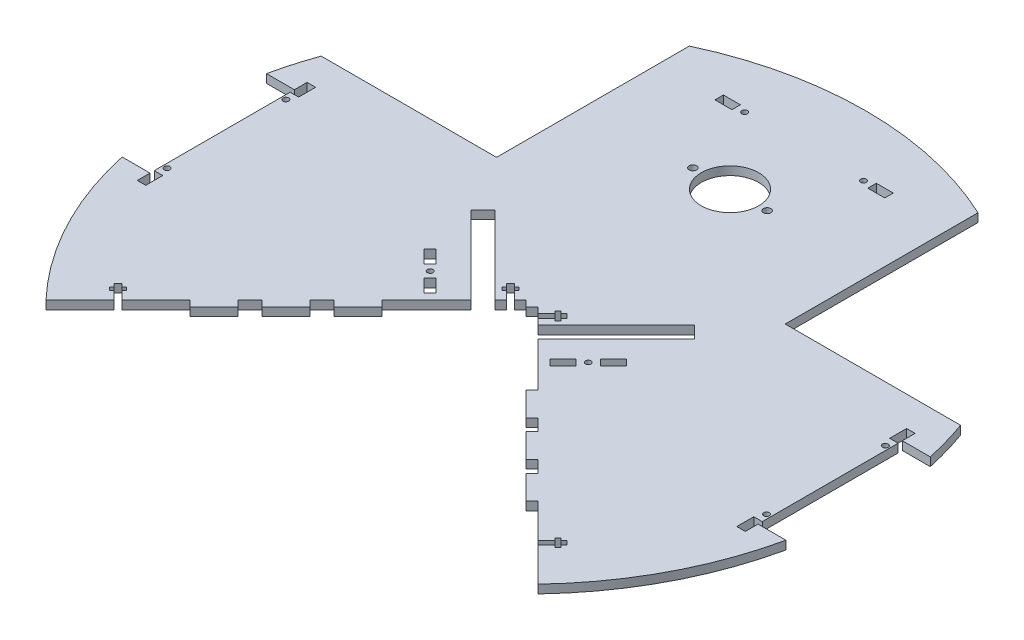
SolidWorks part; units mm, degrees
ref_plane "Front Plane" through (0, 0, 0) normal (0, 0, 1) x (1, 0, 0)
ref_plane "Top Plane" through (0, 0, 0) normal (0, 1, 0) x (1, 0, 0)
ref_plane "Right Plane" through (0, 0, 0) normal (1, 0, 0) x (0, 0, -1)
sketch "Sketch1" plane through (0, 0, 0) normal (0, 1, 0) x (1, 0, 0)
  circle A0 centre (0, 0) radius 254
  dimension "D1" = 508
extrude "Base Plate" add sketch "Sketch1" along normal blind 6.35
sketch "Sketch2" plane through (0, 6.35, 0) normal (0, 1, 0) x (1, 0, 0)
  line L0 (0, 0) -> (-179.6051, -179.6051)
  line L1 (0, -36.2008) -> (0, -54.9716) construction
  line L2 (0, 0) -> (179.6051, -179.6051)
  circle A0 centre (0, 0) radius 254 construction
  arc A1 (-179.6051, -179.6051) -> (179.6051, -179.6051) centre (0, 0) ccw
  dimension "D1" = 254
  dimension "D2" = 45
extrude "V Funnel Cut" cut sketch "Sketch2" against normal through all
sketch "Sketch4" plane through (0, 6.35, 0) normal (0, 1, 0) x (1, 0, 0)
  line L0 (0, 54.2551) -> (0, 121.7464) construction
  line L1 (-251.46, 53.975) -> (-229.87, 53.975)
  line L2 (-254, 51.435) -> (-254, -51.435)
  line L3 (-251.46, -53.975) -> (-229.87, -53.975)
  line L4 (-227.33, 51.435) -> (-227.33, -51.435)
  line L5 (-17.8666, 0) -> (24.1783, 0) construction
  line L6 (-254, -69.5481) -> (-254, -224.3367) construction
  line L8 (-254, 53.975) -> (-227.33, 53.975)
  line L9 (-254, 53.975) -> (-254, -53.975)
  line L10 (-254, -53.975) -> (-227.33, -53.975)
  line L11 (-227.33, 53.975) -> (-227.33, -53.975)
  arc A0 (-251.46, -53.975) -> (-254, -51.435) centre (-251.46, -51.435) cw
  arc A1 (-229.87, -53.975) -> (-227.33, -51.435) centre (-229.87, -51.435) ccw
  arc A2 (-227.33, 51.435) -> (-229.87, 53.975) centre (-229.87, 51.435) ccw
  arc A3 (-251.46, 53.975) -> (-254, 51.435) centre (-251.46, 51.435) ccw
  arc A4 (179.6051, -179.6051) -> (-179.6051, -179.6051) centre (0, 0) ccw construction
  arc M13 (179.6051, -179.6051) -> (-179.6051, -179.6051) centre (0, 0) ccw
  dimension "D5" = 2.54
  dimension "D4" = 2.54
  dimension "D1" = 26.67
  dimension "D3" = 107.95
extrude "Wheel Hole Slot" cut sketch "Sketch4" against normal through all contours A3 L8 L9 | L1 A3 L2 M13 | L4 A2 L1 L3 A1 M13 | A2 L11 L8 | A0 L3 L2 M13 | L10 A0 L9 | A1 L10 L11 region at (-253.4326, 6.35, -53.4076) region at (-252.2473, 6.35, -40.3381) region at (-239.7752, 6.35, 0) region at (-227.8974, 6.35, -53.4076) region at (-252.2473, 6.35, 40.3381) region at (-253.4326, 6.35, 53.4076) region at (-227.8974, 6.35, 53.4076)
mirror "Wheel Slot Mirror" about plane through (0, 0, 0) normal (1, 0, 0) of "Wheel Hole Slot"
sketch "Sketch6" plane through (0, 6.35, 0) normal (0, 1, 0) x (1, 0, 0)
  line L0 (-35.921, -35.921) -> (-20.8354, -51.0067) construction
  line L1 (0, 0) -> (-179.6051, -179.6051) construction
  line L2 (179.6051, -179.6051) -> (0, 0) construction
  line B0 (-61.3685, -5.9835) -> (-71.1005, 3.7485)
  line B1 (-61.3685, -5.9835) -> (-65.8586, -10.4736)
  line B2 (-71.1005, 3.7485) -> (-75.5906, -0.7416)
  line B3 (-65.8586, -10.4736) -> (-75.5906, -0.7416)
  line B4 (-52.3882, -14.9637) -> (-42.6562, -24.6957)
  line B5 (-56.8783, -19.4538) -> (-47.1463, -29.1858)
  line B6 (-42.6562, -24.6957) -> (-47.1463, -29.1858)
  line B7 (-52.3882, -14.9637) -> (-56.8783, -19.4538)
  circle B8 centre (-59.1234, -12.7186) radius 2.0955
  dimension "D1" = 50.8
  dimension "D2" = 12.7
sketch_block_instance "BoltTab-1"
sketch_block "BoltTab" parameters "D1"=4.191, "D2"=6.35, "D3"=6.35
extrude "Arm Post Connector" cut sketch "Sketch6" against normal through all
mirror "Arm Post Connector Mirror" about plane through (0, 0, 0) normal (1, 0, 0) of "Arm Post Connector"
sketch "Sketch8" plane through (0, 0, 0) normal (0, -1, 0) x (1, 0, 0)
  line L0 (-227.33, -63.5) -> (-227.33, -50.8) construction
  line L1 (-227.33, -63.5) -> (-220.98, -63.5) construction
  line L2 (-220.98, -63.5) -> (-220.98, -50.8) construction
  line L3 (-227.33, -50.8) -> (-220.98, -50.8) construction
  line L4 (-227.33, -63.5) -> (-227.33, -50.8)
  line L5 (-227.33, -63.5) -> (-220.98, -63.5)
  line L6 (-220.98, -63.5) -> (-220.98, -50.8)
  line L7 (-227.33, -50.8) -> (-220.98, -50.8)
  line L8 (-227.33, 50.8) -> (-220.98, 50.8) construction
  line L9 (-227.33, 63.5) -> (-227.33, 50.8) construction
  line L10 (-220.98, 63.5) -> (-220.98, 50.8) construction
  line L11 (-227.33, 63.5) -> (-220.98, 63.5) construction
  line L12 (-227.33, 50.8) -> (-220.98, 50.8)
  line L13 (-227.33, 63.5) -> (-227.33, 50.8)
  line L14 (-220.98, 63.5) -> (-220.98, 50.8)
  line L15 (-227.33, 63.5) -> (-220.98, 63.5)
  line L16 (-227.33, -46.5836) -> (-220.98, -46.5836) construction
  line L17 (-227.33, -42.3164) -> (-220.98, -42.3164) construction
  line L18 (-227.33, -46.5836) -> (-220.98, -46.5836) construction
  line L19 (-227.33, -42.3164) -> (-220.98, -42.3164) construction
  line L20 (-224.155, -42.3164) -> (-224.155, -46.5836) construction
  line L21 (-227.33, 42.3164) -> (-220.98, 42.3164) construction
  line L22 (-227.33, 46.5836) -> (-220.98, 46.5836) construction
  line L23 (-227.33, 42.3164) -> (-220.98, 42.3164) construction
  line L24 (-227.33, 46.5836) -> (-220.98, 46.5836) construction
  line L25 (-224.155, 42.3164) -> (-224.155, 46.5836) construction
  circle A0 centre (-224.155, -44.45) radius 2.1336
  circle A1 centre (-224.155, 44.45) radius 2.1336
extrude "Motor Mount Connector" cut sketch "Sketch8" against normal through all
mirror "Motor Mount Connector Mirror" about plane through (0, 0, 0) normal (1, 0, 0) of "Motor Mount Connector"
sketch "Sketch9" plane through (0, 0, 0) normal (0, -1, 0) x (1, 0, 0)
  line L0 (-63.5, -204.6423) -> (-63.5, -210.9923) construction
  line L1 (-63.5, -204.6423) -> (-50.8, -204.6423) construction
  line L2 (-50.8, -204.6423) -> (-50.8, -210.9923) construction
  line L3 (-63.5, -210.9923) -> (-50.8, -210.9923) construction
  line L4 (-63.5, -204.6423) -> (-63.5, -210.9923)
  line L5 (-63.5, -204.6423) -> (-50.8, -204.6423)
  line L6 (-50.8, -204.6423) -> (-50.8, -210.9923)
  line L7 (-63.5, -210.9923) -> (-50.8, -210.9923)
  line L8 (-46.5836, -204.6423) -> (-46.5836, -210.9923) construction
  line L9 (-42.3164, -204.6423) -> (-42.3164, -210.9923) construction
  line L10 (-46.5836, -204.6423) -> (-46.5836, -210.9923) construction
  line L11 (-42.3164, -204.6423) -> (-42.3164, -210.9923) construction
  line L12 (-46.5836, -207.8173) -> (-42.3164, -207.8173) construction
  line L13 (42.3164, -204.6423) -> (42.3164, -210.9923) construction
  line L14 (46.5836, -204.6423) -> (46.5836, -210.9923) construction
  line L15 (42.3164, -204.6423) -> (42.3164, -210.9923) construction
  line L16 (46.5836, -204.6423) -> (46.5836, -210.9923) construction
  line L17 (50.8, -210.9923) -> (63.5, -210.9923)
  line L18 (63.5, -210.9923) -> (63.5, -204.6423)
  line L19 (63.5, -204.6423) -> (50.8, -204.6423)
  line L20 (50.8, -204.6423) -> (50.8, -210.9923)
  line L21 (50.8, -210.9923) -> (63.5, -210.9923)
  line L22 (63.5, -210.9923) -> (63.5, -204.6423)
  line L23 (63.5, -204.6423) -> (50.8, -204.6423)
  line L24 (50.8, -204.6423) -> (50.8, -210.9923)
  line L25 (42.3164, -207.8173) -> (46.5836, -207.8173) construction
  circle A0 centre (-44.45, -207.8173) radius 2.1336
  circle A1 centre (44.45, -207.8173) radius 2.1336
  dimension "D1" = 0
extrude "Back Mount Connector" cut sketch "Sketch9" against normal through all
sketch "Sketch11" plane through (0, 6.35, 0) normal (0, 1, 0) x (1, 0, 0)
  line L0 (0, 61.4305) -> (0, 100.7164) construction
  line L1 (-82.8279, 254) -> (68.7629, 254) construction
  circle A0 centre (0, 152.4) radius 21.463
  circle A2 centre (27.7813, 152.4) radius 2.7781 construction
  circle A3 centre (-27.7813, 152.4) radius 2.7781 construction
  circle A4 centre (27.7813, 152.4) radius 2.7781
  circle A5 centre (-27.7813, 152.4) radius 2.7781
  arc A6 (248.1989, 53.975) -> (-248.1989, 53.975) centre (0, 0) ccw construction
  dimension "D1" = 42.926
  dimension "D2" = 101.6
sketch "Sketch16" plane through (0, 6.35, 0) normal (0, 1, 0) x (1, 0, 0)
  line L0 (20.6696, -20.6696) -> (79.0449, 37.6984)
  line L1 (179.6051, -179.6051) -> (0, 0) construction
  line L3 (20.6696, -20.6696) -> (25.1597, -16.1795) construction
  line L4 (71.8162, 44.9272) -> (13.4445, -13.4445)
  line L5 (0, 0) -> (0, 51.8981) construction
  line L6 (79.0449, 37.6984) -> (71.8162, 44.9272)
  line L7 (20.6696, -20.6696) -> (13.4445, -13.4445)
  line L8 (-79.0449, 37.6984) -> (-71.8162, 44.9272)
  line L9 (-71.8162, 44.9272) -> (-13.4445, -13.4445)
  line L10 (-20.6696, -20.6696) -> (-79.0449, 37.6984)
  line L11 (-20.6696, -20.6696) -> (-13.4445, -13.4445)
  dimension "D1" = 82.55
extrude "Cut-Extrude2" cut sketch "Sketch16" against normal through all
sketch "Sketch17" plane through (0, 6.35, 0) normal (0, 1, 0) x (1, 0, 0)
  line L0 (0, 254) -> (0, 0) construction
  line L1 (-272.7107, 254) -> (-272.7107, 85.7786)
  line L2 (107.9506, 254) -> (272.7107, 254)
  line L3 (107.9506, 254) -> (107.9506, 85.7786)
  line L4 (107.9506, 85.7786) -> (272.7107, 85.7786)
  line L5 (272.7107, 254) -> (272.7107, 85.7786)
  line L6 (-107.9506, 85.7786) -> (-272.7107, 85.7786)
  line L7 (-107.9506, 254) -> (-107.9506, 85.7786)
  line L8 (-107.9506, 254) -> (-272.7107, 254)
  arc A0 (248.1989, 53.975) -> (-248.1989, 53.975) centre (0, 0) ccw construction
extrude "Cut-Extrude4" cut sketch "Sketch17" against normal through all
extrude "Caster Wheel Hole" cut sketch "Sketch11" against normal through all
sketch "Sketch12" plane through (0, 0, 0) normal (0.7071, 0, 0.7071) x (0.7071, 0, -0.7071)
  line L0 (-177.8, 6.35) -> (-177.8, 0) construction
  line L1 (-254, 6.35) -> (-177.8, 6.35)
  line L2 (-254, 6.35) -> (-254, 0)
  line L3 (-254, 0) -> (-177.8, 0)
  line L4 (-177.8, 6.35) -> (-177.8, 0)
  line L5 (0, 0) -> (-19.0134, 0) construction
  line L6 (0, 6.35) -> (-19.0134, 6.35) construction
  line L7 (-152.4, 6.35) -> (-139.7, 6.35)
  line L8 (-152.4, 6.35) -> (-152.4, 0)
  line L9 (-152.4, 0) -> (-139.7, 0)
  line L10 (-139.7, 6.35) -> (-139.7, 0)
  line L11 (-152.4, 0) -> (-152.4, 6.35) construction
  line L12 (-139.7, 6.35) -> (-139.7, 0) construction
  line L13 (-114.3, 0) -> (-114.3, 6.35) construction
  line L14 (-114.3, 6.35) -> (-101.6, 6.35)
  line L15 (-114.3, 6.35) -> (-114.3, 0)
  line L16 (-114.3, 0) -> (-101.6, 0)
  line L17 (-101.6, 6.35) -> (-101.6, 0)
  line L18 (-101.6, 6.35) -> (-101.6, 0) construction
  line L19 (-76.2, 0) -> (-76.2, 6.35) construction
  line L20 (-76.2, 6.35) -> (0, 6.35)
  line L21 (-76.2, 6.35) -> (-76.2, 0)
  line L22 (-76.2, 0) -> (0, 0)
  line L23 (0, 6.35) -> (0, 0)
extrude "V Funnel Tabs" cut sketch "Sketch12" against normal blind 6.35
mirror "V Funnel Tab Mirror" about plane through (0, 0, 0) normal (1, 0, 0) of "V Funnel Tabs"
sketch "Sketch13" plane through (0, 6.35, 0) normal (0, 1, 0) x (1, 0, 0)
  line L0 (-11.6893, -11.6893) -> (-20.6696, -20.6696)
  line L1 (-11.6893, -11.6893) -> (-74.5511, 51.1725)
  line L2 (-20.6696, -20.6696) -> (-83.5314, 42.1922)
  line L3 (-74.5511, 51.1725) -> (-83.5314, 42.1922)
  line L4 (-58.3717, -49.3914) -> (-53.8815, -53.8815) construction
  line L8 (-53.8815, -53.8815) -> (-71.842, -71.842) construction
  line L10 (55.6675, -88.0264) -> (50.4158, -82.7747) construction
  line L11 (-137795.0233, 137762.6644) -> (172087.8094, -172120.1683) construction
  dimension "D1" = 88.9
  dimension "D2" = 12.7
extrude "Peg Clearance" cut sketch "Sketch13" against normal through all
mirror "Peg Clearance Mirror" about plane through (0, 0, 0) normal (1, 0, 0) of "Peg Clearance"
sketch "Sketch14" plane through (0, 6.35, 0) normal (0, 1, 0) x (1, 0, 0)
  line L0 (-30.6253, 18.936) -> (5.9619, -17.6512) construction
  line L1 (-16.1795, -7.1992) -> (-4.4901, 4.4901) construction
  line L3 (0, 0) -> (-4.4901, 4.4901) construction
  line L4 (-16.1795, -7.1992) -> (-74.5511, 51.1725) construction
  line B0 (-11.8435, -2.8632) -> (-8.8261, 0.1541)
  line B1 (-17.2675, 8.5956) -> (-15.6331, 10.23)
  line B2 (-15.6331, 10.23) -> (-13.3881, 7.9849)
  line B3 (-13.3881, 7.9849) -> (-15.0225, 6.3505)
  line B4 (-15.0225, 6.3505) -> (-8.8261, 0.1541)
  line B5 (-17.2675, 8.5956) -> (-19.6024, 10.9305)
  line B6 (-19.6024, 10.9305) -> (-22.6198, 7.9131)
  line B7 (-20.2849, 5.5782) -> (-22.6198, 7.9131)
  line B8 (-18.0398, 3.3332) -> (-11.8435, -2.8632)
  line B9 (-19.6743, 1.6988) -> (-18.0398, 3.3332)
  line B10 (-21.9193, 3.9438) -> (-19.6743, 1.6988)
  line B11 (-20.2849, 5.5782) -> (-21.9193, 3.9438)
sketch_block_instance "TSlot-1"
sketch_block "TSlot" parameters "D1"=3.302, "D2"=3.175
extrude "V Funnel T Slot 1" cut sketch "Sketch14" against normal through all
sketch "Sketch15" plane through (0, 6.35, 0) normal (0, 1, 0) x (1, 0, 0)
  line L0 (-123.3007, -182.028) -> (-191.14, -114.1887) construction
  line L1 (-130.2137, -121.2335) -> (-125.7236, -125.7236) construction
  line L2 (-179.6051, -179.6051) -> (-184.0953, -175.115) construction
  line L3 (-184.0953, -175.115) -> (-176.6237, -167.6434) construction
  line B0 (-158.6632, -149.6829) -> (-155.6458, -146.6655)
  line B1 (-164.0872, -138.2241) -> (-162.4528, -136.5897)
  line B2 (-162.4528, -136.5897) -> (-160.2078, -138.8348)
  line B3 (-160.2078, -138.8348) -> (-161.8422, -140.4692)
  line B4 (-161.8422, -140.4692) -> (-155.6458, -146.6655)
  line B5 (-164.0872, -138.2241) -> (-166.4221, -135.8892)
  line B6 (-166.4221, -135.8892) -> (-169.4395, -138.9066)
  line B7 (-167.1046, -141.2415) -> (-169.4395, -138.9066)
  line B8 (-164.8595, -143.4865) -> (-158.6632, -149.6829)
  line B9 (-166.4939, -145.1209) -> (-164.8595, -143.4865)
  line B10 (-168.739, -142.8759) -> (-166.4939, -145.1209)
  line B11 (-167.1046, -141.2415) -> (-168.739, -142.8759)
sketch_block_instance "TSlot-3"
extrude "V Funnel T Slot 2" cut sketch "Sketch15" against normal through all
mirror "Mirror1" about plane through (0, 0, 0) normal (1, 0, 0) of "V Funnel T Slot 2", "V Funnel T Slot 1"
